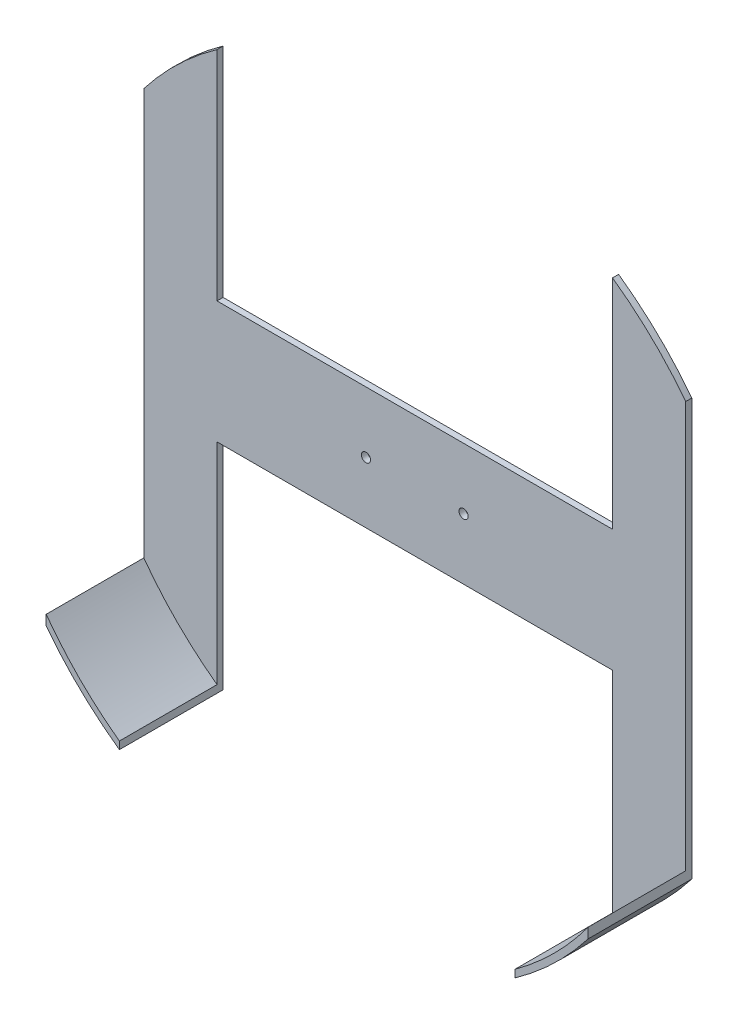
SolidWorks part; units mm, degrees
material "6061 Alloy"
ref_plane "Front Plane" through (0, 0, 0) normal (0, 0, 1) x (1, 0, 0)
ref_plane "Top Plane" through (0, 0, 0) normal (0, 1, 0) x (1, 0, 0)
ref_plane "Right Plane" through (0, 0, 0) normal (1, 0, 0) x (0, 0, -1)
sketch "Sketch1" plane through (0, 0, 0) normal (0, 0, 1) x (1, 0, 0)
  line L1 (-140.9655, 145.0225) -> (-102.8655, 145.0225)
  line L2 (-140.9655, 145.0225) -> (-140.9655, -145.0225)
  line L3 (-140.9655, -145.0225) -> (-102.8655, -145.0225)
  line L4 (-102.8655, 145.0225) -> (-102.8655, -145.0225)
  line L5 (-140.9655, 145.0225) -> (-102.8655, -145.0225) construction
  line L6 (-140.9655, -145.0225) -> (-102.8655, 145.0225) construction
  line L7 (-140.9655, 31.75) -> (140.9655, 31.75)
  line L8 (-140.9655, 31.75) -> (-140.9655, -31.75)
  line L9 (-140.9655, -31.75) -> (140.9655, -31.75)
  line L10 (140.9655, 31.75) -> (140.9655, -31.75)
  line L11 (-140.9655, 31.75) -> (140.9655, -31.75) construction
  line L12 (-140.9655, -31.75) -> (140.9655, 31.75) construction
  line L13 (102.8655, 145.0225) -> (140.9655, 145.0225)
  line L14 (102.8655, 145.0225) -> (102.8655, -145.0225)
  line L15 (102.8655, -145.0225) -> (140.9655, -145.0225)
  line L16 (140.9655, 145.0225) -> (140.9655, -145.0225)
  line L17 (102.8655, 145.0225) -> (140.9655, -145.0225) construction
  line L18 (102.8655, -145.0225) -> (140.9655, 145.0225) construction
  circle A0 centre (0, 0) radius 177.8
  circle A1 centre (25.4, 0) radius 2.3813
  circle A2 centre (-25.4, 0) radius 2.3813
  circle A3 centre (0, 0) radius 25.4 construction
  point P3 (-121.9155, 0)
  point P12 (121.9155, 0)
  dimension "D1" = 355.6
  dimension "D5" = 50.8
  dimension "D6" = 4.7625
  dimension "D7" = 4.7625
  dimension "D2" = 38.1
  dimension "D3" = 38.1
  dimension "D4" = 63.5
extrude "Boss-Extrude1" add sketch "Sketch1" along normal blind 3.175 contours L4 A0 L2 L7 | L2 L9 L4 L7 | L14 L7 L4 L9 A2 A1 | L2 A0 L4 L9 | L16 A0 L14 L7 | L7 L14 L9 L10 | L14 A0 L16 L9 region at (-120.723, 80.7079, 0) region at (0, 0, 0) region at (-121.9155, 0, 0) region at (120.723, 80.7079, 0) region at (-120.723, -80.7079, 0) region at (121.9155, 0, 0) region at (120.723, -80.7079, 0)
sketch "Sketch2" plane through (0, 0, 3.175) normal (0, 0, 1) x (1, 0, 0)
  line L0 (-140.9655, -103.066) -> (-140.9655, -108.3585)
  line L1 (-140.9655, 108.3585) -> (-140.9655, -108.3585) construction
  line L2 (-102.8655, -141.1119) -> (-102.8655, -145.0225)
  line L3 (102.8655, -141.1119) -> (102.8655, -145.0225)
  line L4 (102.8655, -31.75) -> (102.8655, -145.0225) construction
  line L5 (140.9655, -103.066) -> (140.9655, -108.3585)
  line L6 (140.9655, 108.3585) -> (140.9655, -108.3585) construction
  line L7 (-102.8655, -31.75) -> (-102.8655, -145.0225) construction
  circle A0 centre (0, 0) radius 177.8
  circle A1 centre (0, 0) radius 174.625
  line M3 (-140.9655, 108.3585) -> (-140.9655, -108.3585)
  arc M4 (-140.9655, -108.3585) -> (-102.8655, -145.0225) centre (0, 0) ccw
  line M5 (-102.8655, -145.0225) -> (-102.8655, -31.75)
  line M7 (102.8655, -31.75) -> (102.8655, -145.0225)
  arc M8 (102.8655, -145.0225) -> (140.9655, -108.3585) centre (0, 0) ccw
  line M9 (140.9655, -108.3585) -> (140.9655, 108.3585)
  dimension "D1" = 355.6
  dimension "D2" = 349.25
extrude "Boss-Extrude2" add sketch "Sketch2" along normal blind 50.8 contours A1 M3 M4 M5 | A1 M7 M8 M9 region at (-122.8631, -125.3578, 3.175) region at (122.8631, -125.3578, 3.175)
